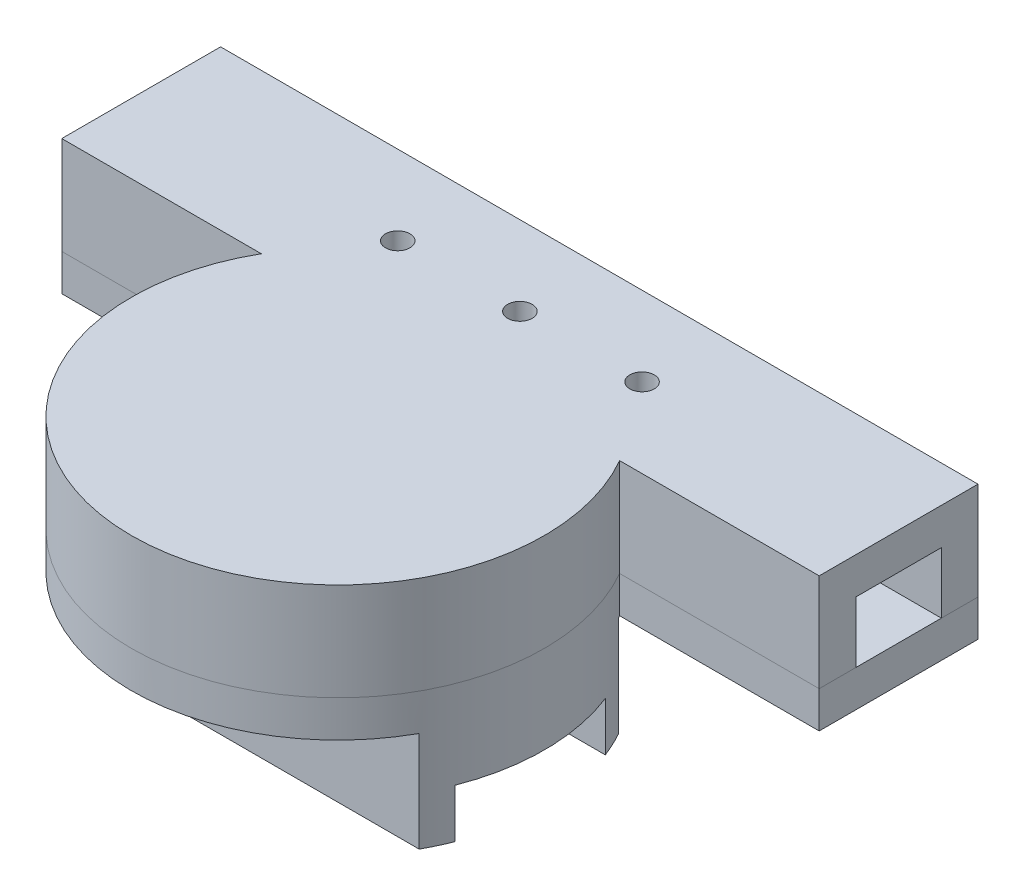
SolidWorks part; units mm, degrees
ref_plane "Front Plane" through (0, 0, 0) normal (0, 0, 1) x (1, 0, 0)
ref_plane "Top Plane" through (0, 0, 0) normal (0, 1, 0) x (1, 0, 0)
ref_plane "Right Plane" through (0, 0, 0) normal (1, 0, 0) x (0, 0, -1)
sketch "Sketch1" plane through (0, 0, 0) normal (0, 1, 0) x (1, 0, 0)
  line L0 (-28, 11.3978) -> (28, 11.3978)
  line L1 (28, 11.3978) -> (28, 18.3978)
  line L2 (28, 18.3978) -> (-28, 18.3978)
  line L3 (-28, 18.3978) -> (-28, 11.3978)
  line L4 (-31, 8.3978) -> (31, 8.3978)
  line L5 (31, 8.3978) -> (31, 21.3978)
  line L6 (31, 21.3978) -> (-31, 21.3978)
  line L7 (-31, 21.3978) -> (-31, 8.3978)
  line L8 (-25, 18.3978) -> (-25, 21.3978)
  line L9 (25, 18.3978) -> (25, 21.3978)
  line L10 (-28, 18.3978) -> (-31, 18.3978)
  line L11 (-28, 11.3978) -> (-31, 11.3978)
  line L12 (28, 11.3978) -> (31, 11.3978)
  line L13 (28, 18.3978) -> (31, 18.3978)
  line L14 (0, 0) -> (0, 50.4739) construction
  line L15 (31, 21.3978) -> (31, 74.3978)
  line L16 (31, 74.3978) -> (-31, 74.3978)
  line L17 (-31, 74.3978) -> (-31, 21.3978)
  line L18 (-25, 21.3978) -> (-25, 71.3978)
  line L19 (-25, 71.3978) -> (25, 71.3978)
  line L20 (25, 71.3978) -> (25, 21.3978)
  circle A0 centre (0, 0) radius 16.9
  circle A1 centre (0, 0) radius 8.3978 construction
  circle A2 centre (0, 0) radius 13.9
  circle A3 centre (0, 0) radius 2
  point P17 (0, 21.3978)
  dimension "D1" = 3
  dimension "D2" = 50
  dimension "D3" = 3
  dimension "D6" = 27.8
  dimension "D11" = 4
  dimension "D4" = 3
  dimension "D5" = 3
  dimension "D7" = 11.3978
  dimension "D8" = 7
  dimension "D9" = 3
  dimension "D10" = 50
extrude "Boss-Extrude1" add sketch "Sketch1" against normal blind 5 contours L10 L2 L8 L6 L7 | A0 L0 L11 L7 L4 | A0 L4 L5 L12 L0 | L2 L13 L5 L6 L9 | A2 L4 A0 | A2 L0 A0 L4 | A2 L4 A0 L0 region at (-22.3167, 0, -9.9292) region at (-11.6173, 0, -9.9549) region at (-28, 0, -19.8978) region at (11.6173, 0, -9.9549) region at (22.3167, 0, -9.9292) region at (-12.8711, 0, -7.9756) region at (28, 0, -19.8978)
extrude "Boss-Extrude2" add sketch "Sketch1<4>" along normal blind 3 contours A2 L4 A0 | A1 | L4 A2 A1 | L4 A2 L0 | L0 A2 | A2 L0 A0 | A2 L0 A0 L4 | A2 L4 A0 L0 | A0 L4 L5 L6 L9 L2 L1 L0 | L2 L9 L6 L8 | A0 L0 L3 L2 L8 L6 L7 L4 | L14 L4 A2 L0 | L14 L0 A2 | L14 A2 L0 A0 | L14 A0 L0 L1 L2 | L13 L1 L12 L5 | L6 L7 L4 L5 region at (-27.4356, 0, -14.8978) region at (-22.3167, 0, -9.9292) region at (0, 0, -14.1208) region at (-11.6173, 0, -9.9549) region at (0, 0, -12.4068) region at (0, 0, -9.818) region at (11.6173, 0, -9.9549) region at (22.3167, 0, -9.9292) region at (-12.8711, 0, -7.9756) region at (0, 0, -19.8978) region at (0, 0, -8.0414) region at (29.5, 0, -14.8978)
sketch "Sketch1<4>" plane through (0, 0, 0) normal (0, 1, 0) x (1, 0, 0) same geometry as "Sketch1"
sketch "Sketch3" plane through (0, -5, 0) normal (0, -1, 0) x (1, 0, 0)
  line L0 (14.6659, -8.3978) -> (31, -8.3978) construction
  line L2 (31, -21.3978) -> (25, -21.3978) construction
  line L3 (-25, -21.3978) -> (-31, -21.3978) construction
  line L4 (-31, -8.3978) -> (-14.6659, -8.3978) construction
  line L11 (14.6659, -8.3978) -> (31, -8.3978)
  line L12 (31, -21.3978) -> (31, -8.3978)
  line L13 (31, -21.3978) -> (25, -21.3978)
  line L14 (-25, -21.3978) -> (-31, -21.3978)
  line L15 (-31, -8.3978) -> (-14.6659, -8.3978)
  line L16 (25, -21.3978) -> (-25, -21.3978)
  line L17 (-31, -21.3978) -> (-31, -8.3978)
  line L22 (-25, -18.3978) -> (-25, -11.3978) construction
  line L23 (-31, -11.3978) -> (-7.9562, -11.3978) construction
  line L24 (-25, -13.3978) -> (-25, -16.3978)
  line L26 (-25, -13.3978) -> (25, -13.3978)
  line L27 (25, -13.3978) -> (25, -16.3978)
  line L28 (25, -16.3978) -> (-25, -16.3978)
  arc A0 (14.6659, -8.3978) -> (-14.6659, -8.3978) centre (0, 0) ccw construction
  arc A1 (14.6659, -8.3978) -> (-14.6659, -8.3978) centre (0, 0) ccw
  circle A4 centre (0, 0) radius 5.35
  circle A5 centre (0, 0) radius 2 construction
  point P21 (-25, -14.8978)
  line M2 (7.9562, -11.3978) -> (31, -11.3978)
  line M3 (31, -11.3978) -> (31, -8.3978)
  line M4 (31, -8.3978) -> (14.6659, -8.3978)
  arc M5 (14.6659, -8.3978) -> (-14.6659, -8.3978) centre (0, 0) ccw
  line M6 (-14.6659, -8.3978) -> (-31, -8.3978)
  line M7 (-31, -8.3978) -> (-31, -11.3978)
  line M8 (-31, -11.3978) -> (-7.9562, -11.3978)
  arc M9 (-7.9562, -11.3978) -> (7.9562, -11.3978) centre (0, 0) cw
  dimension "D2" = 10.7
  dimension "D1" = 3
extrude "Boss-Extrude6" add sketch "Sketch1<7>" along normal blind 3 and the other way blind 2 contours A3 region at (0, 0, 0)
sketch "Sketch1<7>" plane through (0, 0, 0) normal (0, 1, 0) x (1, 0, 0) same geometry as "Sketch1"
extrude "Boss-Extrude7" add sketch "Sketch3" along normal blind 3 separate body contours L27 L28 L24 L17 L14 L16 L13 L12 L26 A4 M8 M2 M9 | M9 M2 M3 M4 M5 M6 M7 M8 | A4 region at (22.8329, -5, -9.0793) region at (0, -5, -7.9127) region at (0, -5, 0)
sketch "Sketch5" plane through (0, 3, 0) normal (0, 1, 0) x (1, 0, 0)
  line L0 (-31, 14.8978) -> (31, 14.8978) construction
  line L1 (-31, 21.3978) -> (-31, 8.3978) construction
  line L2 (31, 8.3978) -> (31, 21.3978) construction
  line L3 (-21, 14.8978) -> (41, 14.8978) construction
  line L4 (-41, 14.8978) -> (21, 14.8978) construction
  circle A0 centre (0, 14.8978) radius 1
  circle A1 centre (10, 14.8978) radius 1
  circle A2 centre (-10, 14.8978) radius 1
  dimension "D1" = 2
  dimension "D2" = 2
extrude "Cut-Extrude1" cut sketch "Sketch5" against normal blind 6
sketch "Sketch6" plane through (0, 0, 0) normal (0, -1, 0) x (1, 0, 0)
  circle A0 centre (10, -14.8978) radius 1 construction
  circle A1 centre (0, -14.8978) radius 1 construction
  circle A2 centre (-10, -14.8978) radius 1 construction
  circle A9 centre (-10, -14.8978) radius 1 construction
  circle A10 centre (0, -14.8978) radius 1 construction
  circle A11 centre (10, -14.8978) radius 1 construction
  circle A12 centre (-10, -14.8978) radius 2
  circle A13 centre (0, -14.8978) radius 2
  circle A14 centre (10, -14.8978) radius 2
  dimension "D1" = 1
extrude "Cut-Extrude2" cut sketch "Sketch6" against normal blind 1 and the other way blind 2.2
extrude "Boss-Extrude9" add sketch "Sketch1<9>" against normal blind 1.6 contours L2 L9 L6 L8 region at (0, 0, -19.8978)
sketch "Sketch1<9>" plane through (0, 0, 0) normal (0, 1, 0) x (1, 0, 0) same geometry as "Sketch1"
extrude "Cut-Extrude3" cut sketch "Sketch3<5>" along normal blind 5 contours A4
sketch "Sketch3<5>" plane through (0, -5, 0) normal (0, -1, 0) x (1, 0, 0) same geometry as "Sketch3"
sketch "Sketch7" [suppressed] plane through (0, 0, 0) normal (0, -1, 0) x (1, 0, 0)
  circle A0 centre (0, 0) radius 5.35
  circle A1 centre (0, 0) radius 2 construction
  dimension "D1" = 10.7
extrude "Cut-Extrude4" [suppressed] cut sketch "Sketch7" against normal blind 5
sketch "Sketch10" [suppressed] plane through (0, -5, 0) normal (0, 1, 0) x (1, 0, 0)
  circle A0 centre (0, 0) radius 2
  circle A1 centre (0, 0) radius 5.35
  circle A2 centre (0, 0) radius 5.35 construction
  dimension "D2" = 4
  dimension "D1" = 0
extrude "Boss-Extrude10" [suppressed] add sketch "Sketch10" along normal blind 2
sketch "Sketch11" plane through (0, -8, 0) normal (0, -1, 0) x (1, 0, 0)
  line L0 (-28.073, -9.8978) -> (27.8555, -9.8978) construction
  line L1 (27.8555, -9.8978) -> (27.8555, -19.8978) construction
  line L2 (27.8555, -19.8978) -> (-28.073, -19.8978) construction
  line L3 (-28.073, -19.8978) -> (-28.073, -9.8978) construction
  line L4 (31, -21.3978) -> (-31, -21.3978) construction
  line L5 (31, -8.3978) -> (14.6659, -8.3978) construction
  circle A0 centre (-28.073, -9.8978) radius 0.75
  circle A1 centre (27.8555, -9.8978) radius 0.75
  circle A2 centre (27.8555, -19.8978) radius 0.75
  circle A3 centre (-28.073, -19.8978) radius 0.75
  circle A4 centre (0, 15.2713) radius 0.75
  circle A5 centre (27.8555, -19.8978) radius 1.25
  circle A6 centre (27.8555, -9.8978) radius 1.25
  circle A7 centre (-28.073, -19.8978) radius 1.25
  circle A8 centre (-28.073, -9.8978) radius 1.25
  circle A9 centre (0, 15.2713) radius 1.25
  dimension "D1" = 1.5
  dimension "D2" = 1.5
  dimension "D3" = 1.5
  dimension "D4" = 0.5
extrude "Cut-Extrude5" cut sketch "Sketch11" against normal blind 6 contours A2 | A1 | A4 | A0 | A3
sketch "Sketch12" plane through (0, -8, 0) normal (0, -1, 0) x (1, 0, 0)
  line L0 (19.2528, -0.002) -> (-8.75, -0.002) construction
  line L1 (21.2528, -8.15) -> (-10.75, -8.15)
  line L2 (-10.75, 8.15) -> (21.2528, 8.15)
  line L3 (15.9249, 6.15) -> (-9.922, 6.15) construction
  line L4 (13.4662, -6.15) -> (-12.4377, -6.15) construction
  line L5 (21.2528, 8.15) -> (21.2528, 0.498)
  line L6 (21.2528, -0.502) -> (21.2528, -8.15)
  line L7 (-10.75, 8.15) -> (-10.75, 0.498)
  line L8 (-10.75, -0.502) -> (-10.75, -8.15)
  line L9 (-9.8956, -0.502) -> (-10.75, -0.502)
  line L10 (-10.75, 0.498) -> (-9.8956, 0.498)
  line L11 (5.75, 2.5) -> (5.1781, 2.5) construction
  line L12 (5.1781, -2.5) -> (5.75, -2.5) construction
  line L13 (5.1781, 2.5) -> (5.75, 2.5) construction
  line L14 (5.75, -2.5) -> (5.1781, -2.5) construction
  line L15 (20.3985, 0.498) -> (21.2528, 0.498)
  line L16 (21.2528, -0.502) -> (20.3985, -0.502)
  line L17 (5.75, 2.9) -> (5.4233, 2.9)
  line L18 (5.4233, -2.9) -> (5.75, -2.9)
  arc A0 (-9.8956, -0.502) -> (-9.8956, 0.498) centre (-8.75, -0.002) ccw
  arc A1 (0, 5.75) -> (-5.75, 0) centre (0, 0) ccw construction
  arc A2 (5.75, -2.5) -> (5.75, 2.5) centre (5.75, 0) ccw construction
  arc A3 (5.1781, 2.5) -> (5.1781, -2.5) centre (0, 0) ccw construction
  arc A4 (0, -5.75) -> (5.1781, -2.5) centre (0, 0) ccw construction
  arc A5 (5.1781, 2.5) -> (0, 5.75) centre (0, 0) ccw construction
  arc A6 (5.75, -2.5) -> (5.75, 2.5) centre (5.75, 0) ccw construction
  arc A7 (20.3985, 0.498) -> (20.3985, -0.502) centre (19.2528, -0.002) ccw
  arc A8 (5.4233, 2.9) -> (5.4233, -2.9) centre (0, 0) ccw
  arc A9 (5.75, -2.9) -> (5.75, 2.9) centre (5.75, 0) ccw
  circle A10 centre (0, 0) radius 2 construction
  arc A11 (14.6659, -8.3978) -> (-14.6659, -8.3978) centre (0, 0) ccw construction
  arc A12 (14.805, -8.15) -> (14.805, 8.15) centre (0, 0) ccw
  arc M9 (14.6659, -8.3978) -> (-14.6659, -8.3978) centre (0, 0) ccw
extrude "Boss-Extrude11" add sketch "Sketch12" along normal blind 4.2 contours A0 L9 L8 L1 L2 L7 L10 A9 L18 A8 L17 M9 region at (2.0275, -8, -7.829)
sketch "Sketch13" plane through (0, -12.2, 0) normal (0, -1, 0) x (1, 0, 0)
  line L0 (14.805, -8.15) -> (-10.75, -8.15) construction
  line L1 (-10.75, -0.502) -> (-10.75, -8.15) construction
  line L2 (-10.75, 8.15) -> (-10.75, 0.498) construction
  line L3 (-10.75, 0.498) -> (-9.8956, 0.498) construction
  line L4 (-10.75, 8.15) -> (14.805, 8.15) construction
  line L5 (-9.8956, -0.502) -> (-10.75, -0.502) construction
  line L6 (5.75, 2.9) -> (5.4233, 2.9) construction
  line L7 (5.4233, -2.9) -> (5.75, -2.9) construction
  line L8 (14.805, -8.15) -> (-10.75, -8.15)
  line L9 (-10.75, -0.502) -> (-10.75, -8.15)
  line L10 (-10.75, 8.15) -> (-10.75, 0.498)
  line L11 (-10.75, 0.498) -> (-9.8956, 0.498)
  line L12 (-10.75, 8.15) -> (14.805, 8.15)
  line L13 (-9.8956, -0.502) -> (-10.75, -0.502)
  line L14 (5.75, 2.9) -> (5.4233, 2.9)
  line L15 (5.4233, -2.9) -> (5.75, -2.9)
  line L16 (15.7413, -6.15) -> (-10.75, -6.15)
  line L17 (15.7413, 6.15) -> (-10.75, 6.15)
  arc A0 (-9.8956, -0.502) -> (-9.8956, 0.498) centre (-8.75, -0.002) ccw construction
  arc A1 (14.805, -8.15) -> (14.805, 8.15) centre (0, 0) ccw construction
  arc A2 (5.4233, 2.9) -> (5.4233, -2.9) centre (0, 0) ccw construction
  arc A3 (5.75, -2.9) -> (5.75, 2.9) centre (5.75, 0) ccw construction
  arc A4 (-9.8956, -0.502) -> (-9.8956, 0.498) centre (-8.75, -0.002) ccw
  arc A5 (14.805, -8.15) -> (14.805, 8.15) centre (0, 0) ccw
  arc A6 (5.4233, 2.9) -> (5.4233, -2.9) centre (0, 0) ccw
  arc A7 (5.75, -2.9) -> (5.75, 2.9) centre (5.75, 0) ccw
  arc M5 (5.4233, -2.9) -> (5.4233, 2.9) centre (0, 0) cw
  arc M7 (-9.8956, 0.498) -> (-9.8956, -0.502) centre (-8.75, -0.002) cw
  line M8 (-9.8956, -0.502) -> (-10.75, -0.502)
  line M9 (-10.75, -0.502) -> (-10.75, -8.15)
  line M10 (-10.75, -8.15) -> (14.805, -8.15)
  arc M11 (14.805, -8.15) -> (14.805, 8.15) centre (0, 0) ccw
  line M12 (14.805, 8.15) -> (-10.75, 8.15)
  line M13 (-10.75, 8.15) -> (-10.75, 0.498)
  line M14 (-10.75, 0.498) -> (-9.8956, 0.498)
extrude "Boss-Extrude12" add sketch "Sketch13" along normal blind 4 contours L16 L9 M11 M10 | L17 M11 M12 M13 | L17 L10 L16 M5 M14 M7 M8 M9 region at (2.2763, -12.2, -7.144) region at (-10.5866, -12.2, -3.326) region at (2.2763, -12.2, 7.144)
extrude "Cut-Extrude6" cut sketch "Sketch11<4>" against normal blind 1 contours A5 A2 | A6 A1 | A8 A0 | A7 A3 | A9 A4 region at (26.6408, -8, -19.8978) region at (26.6408, -8, -9.8978) region at (-29.2876, -8, -19.8978) region at (-29.2876, -8, -9.8978) region at (-1.2146, -8, 15.2713)
sketch "Sketch11<4>" plane through (0, -8, 0) normal (0, -1, 0) x (1, 0, 0) same geometry as "Sketch11"
sketch "Sketch14" [suppressed] plane through (0, 3, 0) normal (0, 1, 0) x (1, 0, 0)
  line L2 (5.4233, -2.9) -> (5.75, -2.9)
  line L3 (5.75, 2.9) -> (5.4233, 2.9)
  line L4 (5.4233, -2.9) -> (5.75, -2.9)
  line L5 (5.75, 2.9) -> (5.4233, 2.9)
  line L10 (21.2528, -8.15) -> (21.2528, -0.498)
  line L11 (-10.75, -8.15) -> (21.2528, -8.15)
  line L12 (-10.75, -0.498) -> (-10.75, -8.15)
  line L13 (-9.8956, -0.498) -> (-10.75, -0.498)
  line L14 (-10.75, 0.502) -> (-9.8956, 0.502)
  line L15 (-10.75, 8.15) -> (-10.75, 0.502)
  line L16 (21.2528, 8.15) -> (-10.75, 8.15)
  line L17 (21.2528, 0.502) -> (21.2528, 8.15)
  line L18 (20.3985, 0.502) -> (21.2528, 0.502)
  line L19 (21.2528, -0.498) -> (20.3985, -0.498)
  line L20 (21.2528, -8.15) -> (21.2528, -0.498)
  line L21 (-10.75, -8.15) -> (21.2528, -8.15)
  line L22 (-10.75, -0.498) -> (-10.75, -8.15)
  line L23 (-9.8956, -0.498) -> (-10.75, -0.498)
  line L24 (-10.75, 0.502) -> (-9.8956, 0.502)
  line L25 (-10.75, 8.15) -> (-10.75, 0.502)
  line L26 (21.2528, 8.15) -> (-10.75, 8.15)
  line L27 (21.2528, 0.502) -> (21.2528, 8.15)
  line L28 (20.3985, 0.502) -> (21.2528, 0.502)
  line L29 (21.2528, -0.498) -> (20.3985, -0.498)
  arc A0 (14.805, -8.15) -> (14.805, 8.15) centre (0, 0) ccw construction
  arc A1 (14.805, -8.15) -> (14.805, 8.15) centre (0, 0) ccw
  arc A2 (-9.8956, -0.498) -> (-9.8956, 0.502) centre (-8.75, 0.002) ccw
  arc A3 (20.3985, 0.502) -> (20.3985, -0.498) centre (19.2528, 0.002) ccw
  arc A4 (-9.8956, -0.498) -> (-9.8956, 0.502) centre (-8.75, 0.002) ccw
  arc A5 (20.3985, 0.502) -> (20.3985, -0.498) centre (19.2528, 0.002) ccw
  arc A6 (5.4233, 2.9) -> (5.4233, -2.9) centre (0, 0) ccw
  arc A7 (5.75, -2.9) -> (5.75, 2.9) centre (5.75, 0) ccw
  arc A8 (5.4233, 2.9) -> (5.4233, -2.9) centre (0, 0) ccw
  arc A9 (5.75, -2.9) -> (5.75, 2.9) centre (5.75, 0) ccw
  dimension "D1" = 0
  dimension "D2" = 0
